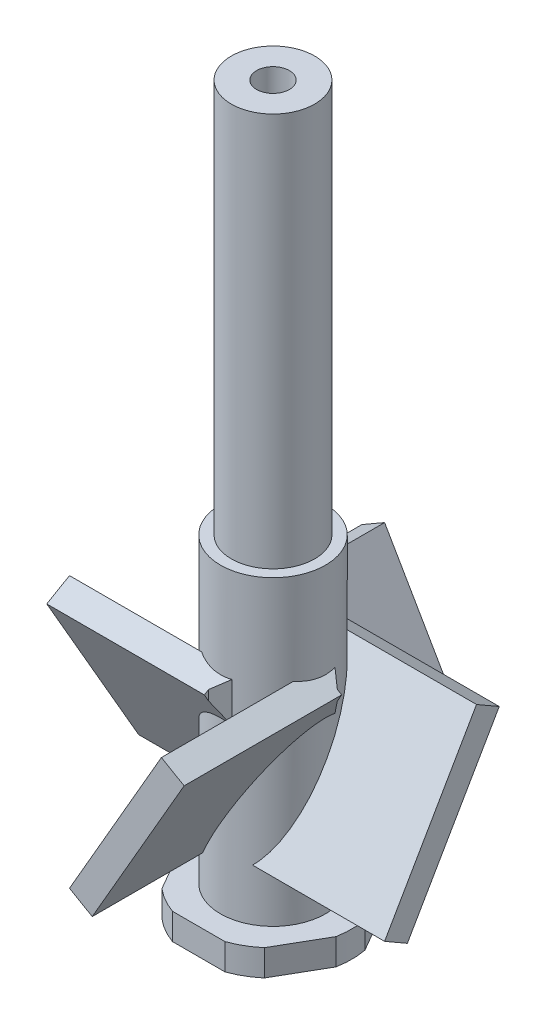
SolidWorks part; units mm, degrees
ref_plane "Front Plane" through (0, 0, 0) normal (0, 0, 1) x (1, 0, 0)
ref_plane "Top Plane" through (0, 0, 0) normal (0, 1, 0) x (1, 0, 0)
ref_plane "Right Plane" through (0, 0, 0) normal (1, 0, 0) x (0, 0, -1)
sketch "Sketch1" plane through (0, 0, 0) normal (0, 1, 0) x (1, 0, 0)
  line L48 (-2, -5.6569) -> (2, -5.6569)
  line L55 (2, -5.6569) -> (2, -17.1569)
  line L62 (2, -17.1569) -> (-2, -17.1569)
  line L69 (-2, -17.1569) -> (-2, -5.6569)
  line L70 (-15.8583, -6.8464) -> (-5.899, -1.0964)
  line L71 (-5.899, -1.0964) -> (-3.899, -4.5605)
  line L72 (-3.899, -4.5605) -> (-13.8583, -10.3105)
  line L73 (-13.8583, -10.3105) -> (-15.8583, -6.8464)
  line L74 (-13.8583, 10.3105) -> (-3.899, 4.5605)
  line L75 (-3.899, 4.5605) -> (-5.899, 1.0964)
  line L76 (-5.899, 1.0964) -> (-15.8583, 6.8464)
  line L77 (-15.8583, 6.8464) -> (-13.8583, 10.3105)
  line L78 (2, 17.1569) -> (2, 5.6569)
  line L79 (2, 5.6569) -> (-2, 5.6569)
  line L80 (-2, 5.6569) -> (-2, 17.1569)
  line L81 (-2, 17.1569) -> (2, 17.1569)
  line L82 (15.8583, 6.8464) -> (5.899, 1.0964)
  line L83 (5.899, 1.0964) -> (3.899, 4.5605)
  line L84 (3.899, 4.5605) -> (13.8583, 10.3105)
  line L85 (13.8583, 10.3105) -> (15.8583, 6.8464)
  line L86 (13.8583, -10.3105) -> (3.899, -4.5605)
  line L87 (3.899, -4.5605) -> (5.899, -1.0964)
  line L88 (5.899, -1.0964) -> (15.8583, -6.8464)
  line L89 (15.8583, -6.8464) -> (13.8583, -10.3105)
  line L90 (-2, 5.6569) -> (-2, 3.4641)
  line L91 (2, 5.6569) -> (2, 3.4641)
  line L92 (3.899, 4.5605) -> (2, 3.4641)
  line L93 (5.899, 1.0964) -> (4, 0)
  line L94 (5.899, -1.0964) -> (4, 0)
  line L95 (3.899, -4.5605) -> (2, -3.4641)
  line L96 (2, -5.6569) -> (2, -3.4641)
  line L97 (-2, -5.6569) -> (-2, -3.4641)
  line L98 (-3.899, -4.5605) -> (-2, -3.4641)
  line L99 (-5.899, -1.0964) -> (-4, 0)
  line L100 (-5.899, 1.0964) -> (-4, 0)
  line L101 (-3.899, 4.5605) -> (-2, 3.4641)
  circle A2 centre (0, 0) radius 4
  arc A3 (2, -5.6569) -> (3.899, -4.5605) centre (0, 0) ccw
  arc A4 (-3.899, -4.5605) -> (-2, -5.6569) centre (0, 0) ccw
  arc A5 (-5.899, 1.0964) -> (-5.899, -1.0964) centre (0, 0) ccw
  arc A6 (-2, 5.6569) -> (-3.899, 4.5605) centre (0, 0) ccw
  arc A7 (3.899, 4.5605) -> (2, 5.6569) centre (0, 0) ccw
  arc A8 (5.899, -1.0964) -> (5.899, 1.0964) centre (0, 0) ccw
  point P9 (0, -5.6569)
  point P31 (0, 0)
  point P32 (0, 0)
  point P33 (0, 0)
  point P46 (0.0289, 0.0554)
  dimension "D1" = 8
  dimension "D2" = 6
  dimension "D3" = 2
  dimension "D4" = 4
  dimension "D5" = 11.5
  dimension "D6" = 6
extrude "Boss-Extrude1" add sketch "Sketch1" along normal blind 25 contours A2
extrude "Boss-Extrude3" add sketch "Sketch1<4>" along normal blind 2 contours L90 A6 L101 | A2 L101 L75 L100 | L100 A5 L99 | A2 L99 L71 L98 | L98 A4 L97 | A2 L97 L48 L96 | L96 A3 L95 | A2 L95 L87 L94 | L94 A8 L93 | A2 L93 L83 L92 | L92 A7 L91 | A2 L91 L79 L90 region at (0, 0, 4.7348) region at (-2.6553, 0, 4.5992) region at (2.6553, 0, 4.5992) region at (-4.1005, 0, 2.3674) region at (4.1005, 0, 2.3674) region at (-5.3107, 0, 0) region at (-4.1005, 0, -2.3674) region at (4.1005, 0, -2.3674) region at (5.3107, 0, 0) region at (-2.6553, 0, -4.5992) region at (0, 0, -4.7348) region at (2.6553, 0, -4.5992)
sketch "Sketch1<4>" plane through (0, 0, 0) normal (0, 1, 0) x (1, 0, 0) same geometry as "Sketch1"
sketch "Sketch2" plane through (0, 25, 0) normal (0, 1, 0) x (1, 0, 0)
  circle A1 centre (0, 0) radius 3.175
  circle A3 centre (0, 0) radius 1.175
  dimension "D1" = 2
  dimension "D2" = 2.35
extrude "Boss-Extrude6" add sketch "Sketch2" along normal blind 30 contours A1
sketch "Sketch3" plane through (0, 55, 0) normal (0, 1, 0) x (1, 0, 0)
  circle A0 centre (0, 0) radius 1.25
  dimension "D1" = 2.5
extrude "Cut-Extrude1" cut sketch "Sketch3" against normal blind 10
sketch "Sketch7" plane through (0, 0, 0) normal (0, 0, 1) x (1, 0, 0)
  line L0 (0, 2) -> (0, 12) construction
  line L1 (-2, 2) -> (2, 2) construction
  line L2 (-3.5, 5.9378) -> (3.5, 18.0622)
  line L3 (3.5, 18.0622) -> (5.2321, 17.0622)
  line L4 (5.2321, 17.0622) -> (-1.7679, 4.9378)
  line L5 (-1.7679, 4.9378) -> (-3.5, 5.9378)
  point P8 (0, 12)
  dimension "D1" = 10
  dimension "D2" = 7
  dimension "D3" = 60
  dimension "D4" = 2
extrude "Boss-Extrude8" add sketch "Sketch7" along normal blind 12
pattern_circular "CirPattern1" count 4 over 360 about axis through (0, 55, 0) along (0, 1, 0) of "Boss-Extrude8"
chamfer "Chamfer1" distance 1 angle 45 4 edges at (0, 16.3509, 4) (-4, 16.3509, 0) (0, 16.3509, -4) (4, 16.3509, 0)
sketch "Sketch8" plane through (0, 45, 0) normal (0, 1, 0) x (1, 0, 0)
  circle A0 centre (0, 0) radius 15
  dimension "D1" = 30
